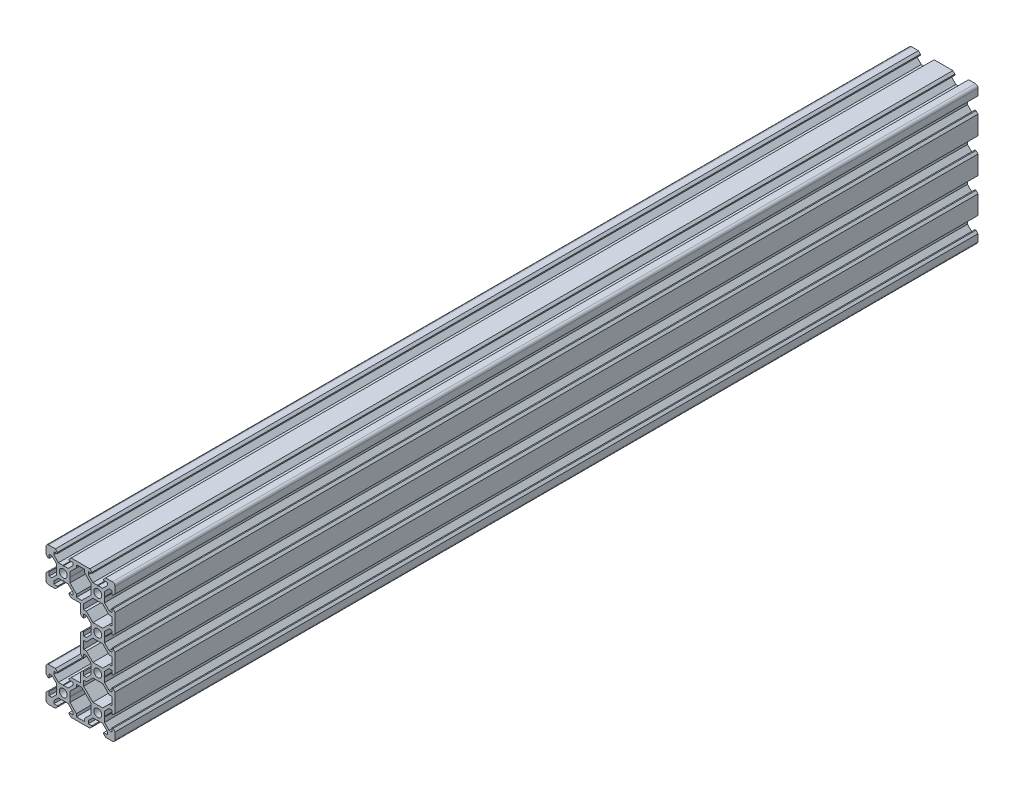
SolidWorks part; units mm, degrees
material "6063-T5"
ref_plane "Front Plane" through (0, 0, 0) normal (0, 0, 1) x (1, 0, 0)
ref_plane "Top Plane" through (0, 0, 0) normal (0, 1, 0) x (1, 0, 0)
ref_plane "Right Plane" through (0, 0, 0) normal (1, 0, 0) x (0, 0, -1)
sketch "Sketch1" plane through (0, 0, 0) normal (0, 0, 1) x (1, 0, 0)
  line L0 (0, 9.9766) -> (0, -9.9766) construction
  line L5 (-10, 10) -> (10, -10) construction
  line L6 (-10, -10) -> (10, 10) construction
  line L7 (-10.0451, 0) -> (10.0451, 0) construction
  line L8 (-4.578, 10) -> (-3.4, 8.822)
  line L9 (-3.4, 8.822) -> (-3.4, 8.202)
  line L10 (-3.4, 8.202) -> (-5.4992, 8.202)
  line L11 (-5.4992, 6.5612) -> (-2.84, 3.902)
  line L12 (-2.84, 3.902) -> (-0.21, 3.902)
  line L13 (-5.4992, 8.202) -> (-5.4992, 6.5612)
  line L14 (-10, 4.578) -> (-8.822, 3.4)
  line L15 (-8.822, 3.4) -> (-8.202, 3.4)
  line L16 (-8.202, 3.4) -> (-8.202, 5.4992)
  line L17 (-8.202, 5.4992) -> (-6.5612, 5.4992)
  line L18 (-6.5612, 5.4992) -> (-3.902, 2.84)
  line L19 (-3.902, 2.84) -> (-3.9017, 0.2097)
  line L20 (3.902, 2.84) -> (3.902, 0.21)
  line L21 (6.5612, 5.4992) -> (3.902, 2.84)
  line L26 (2.84, 3.902) -> (0.2097, 3.9017)
  line L27 (5.4992, 6.5612) -> (2.84, 3.902)
  line L28 (5.4992, 8.202) -> (5.4992, 6.5612)
  line L29 (3.4, 8.202) -> (5.4992, 8.202)
  line L30 (3.4, 8.822) -> (3.4, 8.202)
  line L31 (4.578, 10) -> (3.4, 8.822)
  line L32 (2.84, -3.902) -> (0.21, -3.902)
  line L33 (5.4992, -6.5612) -> (2.84, -3.902)
  line L34 (5.4992, -8.202) -> (5.4992, -6.5612)
  line L35 (3.4, -8.202) -> (5.4992, -8.202)
  line L36 (4.578, -10) -> (3.4, -8.822)
  line L37 (3.4, -8.822) -> (3.4, -8.202)
  line L38 (3.902, -2.84) -> (3.9017, -0.2097)
  line L39 (6.5612, -5.4992) -> (3.902, -2.84)
  line L44 (-3.902, -2.84) -> (-3.902, -0.21)
  line L45 (-6.5612, -5.4992) -> (-3.902, -2.84)
  line L46 (-8.202, -5.4992) -> (-6.5612, -5.4992)
  line L47 (-8.202, -3.4) -> (-8.202, -5.4992)
  line L48 (-10, -4.578) -> (-8.822, -3.4)
  line L49 (-8.822, -3.4) -> (-8.202, -3.4)
  line L50 (-2.84, -3.902) -> (-0.2097, -3.9017)
  line L51 (-5.4992, -6.5612) -> (-2.84, -3.902)
  line L52 (-5.4992, -8.202) -> (-5.4992, -6.5612)
  line L53 (-3.4, -8.202) -> (-5.4992, -8.202)
  line L54 (-3.4, -8.822) -> (-3.4, -8.202)
  line L55 (-4.578, -10) -> (-3.4, -8.822)
  line L56 (-0.21, 3.902) -> (0, 3.692)
  line L57 (0, 3.692) -> (0.2097, 3.9017)
  line L60 (0, -3.692) -> (-0.2097, -3.9017)
  line L61 (0.21, -3.902) -> (0, -3.692)
  line L62 (-3.692, 0) -> (-3.9017, 0.2097)
  line L63 (-3.902, -0.21) -> (-3.692, 0)
  line L64 (-8.5, 10) -> (-4.578, 10)
  line L65 (-10, 8.5) -> (-10, 4.578)
  line L66 (-10, -4.578) -> (-10, -8.5)
  line L67 (-8.5, -10) -> (-4.578, -10)
  line L68 (4.578, -10) -> (10, -10)
  line L71 (15.422, 10) -> (4.578, 10)
  line L80 (6.5612, -5.4992) -> (7.7124, -6.6505)
  line L82 (7.7124, -8.1789) -> (10, -8.1789)
  line L88 (7.7124, -6.6505) -> (7.7124, -8.1789)
  line L90 (8.202, -3.4) -> (8.202, -5.4992) [skipped]
  line L91 (8.202, -5.4992) -> (6.5612, -5.4992) [skipped]
  line L92 (8.822, -3.4) -> (8.202, -3.4) [skipped]
  line L93 (10, -4.578) -> (8.822, -3.4) [skipped]
  line L103 (10, 10) -> (10, -10) construction
  line L106 (10, 10) -> (30, -10) construction
  line L108 (10, -10) -> (30, 10) construction
  line L110 (10, -8.1789) -> (10.74, -8.1789)
  line L112 (10.74, -8.1789) -> (16.098, -2.8209)
  line L114 (11.8211, -10) -> (11.8211, -9.26)
  line L115 (11.8211, -9.26) -> (17.1791, -3.902)
  line L116 (6.5612, 5.4992) -> (7.6221, 6.5602)
  line L125 (7.6221, 6.5602) -> (7.6221, 8.2015)
  line L127 (7.6221, 8.2015) -> (12.3779, 8.2015)
  line L128 (8.202, 5.4992) -> (6.5612, 5.4992) [skipped]
  line L129 (8.202, 3.4) -> (8.202, 5.4992) [skipped]
  line L130 (8.822, 3.4) -> (8.202, 3.4) [skipped]
  line L131 (10, 4.578) -> (8.822, 3.4) [skipped]
  line L134 (16.098, 2.84) -> (16.098, -2.8209)
  line L137 (16.098, 3.902) -> (23.902, -3.902) construction
  line L138 (16.098, -3.902) -> (23.902, 3.902) construction
  line L140 (15.422, 10) -> (16.6, 8.822)
  line L141 (16.6, 8.822) -> (16.6, 8.202)
  line L142 (16.6, 8.202) -> (14.5008, 8.202)
  line L143 (14.5008, 8.202) -> (14.5008, 6.5612)
  line L144 (14.5008, 6.5612) -> (17.16, 3.902)
  line L145 (13.4388, 5.4992) -> (16.098, 2.84)
  line L146 (13.4388, 5.4992) -> (12.3779, 6.5602)
  line L147 (12.3779, 6.5602) -> (12.3779, 8.2015)
  line L148 (25.4992, 6.5612) -> (22.84, 3.902)
  line L149 (26.5612, 5.4992) -> (23.902, 2.84)
  line L150 (23.4, 8.822) -> (23.4, 8.202)
  line L151 (28.822, 3.4) -> (28.202, 3.4)
  line L152 (28.202, 3.4) -> (28.202, 5.4992)
  line L153 (30, 4.578) -> (28.822, 3.4)
  line L154 (28.202, 5.4992) -> (26.5612, 5.4992)
  line L155 (24.578, 10) -> (23.4, 8.822)
  line L156 (23.4, 8.202) -> (25.4992, 8.202)
  line L157 (25.4992, 8.202) -> (25.4992, 6.5612)
  line L158 (28.5, 10) -> (24.578, 10)
  line L159 (30, 8.5) -> (30, 4.578)
  line L160 (10.0451, 0) -> (29.9549, 0) construction
  line L161 (25.4992, -6.5612) -> (22.84, -3.902)
  line L167 (30, -15.422) -> (30, -4.578)
  line L168 (28.202, -5.4992) -> (26.5612, -5.4992)
  line L169 (30, -4.578) -> (28.822, -3.4)
  line L170 (28.202, -3.4) -> (28.202, -5.4992)
  line L171 (28.822, -3.4) -> (28.202, -3.4)
  line L172 (26.5612, -5.4992) -> (23.902, -2.84)
  line L173 (17.16, 3.902) -> (19.79, 3.902)
  line L174 (17.1791, -3.902) -> (22.84, -3.902)
  line L175 (23.902, -2.84) -> (23.902, -0.21)
  line L176 (23.898, -20.21) -> (23.898, -22.8606)
  line L177 (28.2471, -7.6231) -> (28.2471, -12.3769)
  line L178 (14.5008, -13.4388) -> (17.16, -16.098)
  line L179 (25.4992, -6.5612) -> (26.5612, -7.6231)
  line L180 (26.5612, -7.6231) -> (28.2471, -7.6231)
  line L181 (25.5443, -13.4388) -> (22.8851, -16.098)
  line L185 (23.898, -17.1394) -> (23.898, -19.79)
  line L186 (16.098, -16.1) -> (23.898, -23.9) construction
  line L187 (16.098, -23.9) -> (23.898, -16.1) construction
  line L188 (26.5367, -14.5008) -> (23.8775, -17.16)
  line L189 (28.822, -16.6) -> (28.1775, -16.6)
  line L190 (28.1775, -16.6) -> (28.1775, -14.5008)
  line L191 (30, -15.422) -> (28.822, -16.6)
  line L192 (28.1775, -14.5008) -> (26.5367, -14.5008)
  line L193 (26.6063, -12.3769) -> (28.2471, -12.3769)
  line L194 (25.5443, -13.4388) -> (26.6063, -12.3769)
  line L195 (14.5008, -13.4388) -> (13.3495, -12.2876)
  line L196 (11.8211, -12.2876) -> (11.8211, -10)
  line L197 (13.3495, -12.2876) -> (11.8211, -12.2876)
  line L198 (13.4388, -14.5008) -> (16.098, -17.16)
  line L199 (11.798, -14.5008) -> (13.4388, -14.5008)
  line L200 (11.798, -16.6) -> (11.798, -14.5008)
  line L201 (11.178, -16.6) -> (11.798, -16.6)
  line L202 (10, -15.422) -> (11.178, -16.6)
  line L203 (10, -15.422) -> (10, -10)
  line L204 (17.16, -16.098) -> (22.8851, -16.098)
  line L205 (3.902, 0.21) -> (3.9017, -0.2097)
  line L206 (16.098, -20) -> (23.898, -20) construction
  line L207 (13.4388, -25.4992) -> (16.098, -22.84)
  line L208 (11.798, -25.4992) -> (13.4388, -25.4992)
  line L209 (11.798, -23.4) -> (11.798, -25.4992)
  line L210 (11.178, -23.4) -> (11.798, -23.4)
  line L211 (10, -24.578) -> (11.178, -23.4)
  line L212 (10, -24.578) -> (10, -35.422)
  line L213 (11.8211, -27.7124) -> (11.8211, -32.2876)
  line L214 (13.3495, -27.7124) -> (11.8211, -27.7124)
  line L215 (14.5008, -26.5612) -> (13.3495, -27.7124)
  line L216 (14.5008, -26.5612) -> (17.16, -23.902)
  line L217 (25.5443, -26.5612) -> (22.8851, -23.902)
  line L218 (28.2471, -32.3769) -> (28.2471, -27.6231)
  line L219 (26.6063, -27.6231) -> (28.2471, -27.6231)
  line L220 (25.5443, -26.5612) -> (26.6063, -27.6231)
  line L221 (26.5367, -25.4992) -> (23.8775, -22.84)
  line L222 (28.1775, -25.4992) -> (26.5367, -25.4992)
  line L223 (28.822, -23.4) -> (28.1775, -23.4)
  line L224 (30, -24.578) -> (28.822, -23.4)
  line L225 (28.1775, -23.4) -> (28.1775, -25.4992)
  line L226 (30, -24.578) -> (30, -35.422)
  line L229 (17.16, -23.902) -> (22.8851, -23.902)
  line L230 (20, -3.902) -> (20, 3.902) construction
  line L231 (3.902, 0.21) -> (3.692, 0) [skipped]
  line L232 (3.692, 0) -> (3.9017, -0.2097) [skipped]
  line L233 (23.902, 0.21) -> (23.692, 0)
  line L234 (23.692, 0) -> (23.902, -0.21)
  line L235 (19.79, 3.902) -> (20, 3.692)
  line L236 (20, 3.692) -> (20.21, 3.902)
  line L237 (20.21, 3.902) -> (22.84, 3.902)
  line L238 (23.902, 0.21) -> (23.902, 2.84)
  line L239 (23.898, -19.79) -> (23.688, -20)
  line L240 (23.688, -20) -> (23.898, -20.21)
  line L241 (16.102, -19.79) -> (16.312, -20)
  line L242 (16.312, -20) -> (16.102, -20.21)
  line L243 (16.102, -19.79) -> (16.098, -17.16)
  line L244 (16.102, -20.21) -> (16.098, -22.84)
  line L246 (16.098, -40) -> (23.898, -40) construction
  line L247 (16.098, -36.1) -> (23.898, -43.9) construction
  line L248 (16.098, -43.9) -> (23.898, -36.1) construction
  line L250 (16.098, -56.098) -> (23.902, -63.902) construction
  line L251 (16.098, -63.902) -> (23.902, -56.098) construction
  line L252 (10, -50) -> (30, -70) construction
  line L253 (10, -70) -> (30, -50) construction
  line L254 (10, -70) -> (10, -50) construction
  line L256 (-10, -50) -> (10, -70) construction
  line L257 (-10, -70) -> (10, -50) construction
  line L259 (16.102, -39.79) -> (16.098, -37.16)
  line L260 (16.102, -40.21) -> (16.098, -42.84)
  line L261 (16.312, -40) -> (16.102, -39.79)
  line L262 (16.102, -40.21) -> (16.312, -40)
  line L263 (23.688, -40) -> (23.898, -39.79)
  line L264 (23.898, -40.21) -> (23.688, -40)
  line L265 (23.902, -60.21) -> (23.902, -62.84)
  line L266 (20.21, -63.902) -> (22.84, -63.902)
  line L267 (20, -63.692) -> (20.21, -63.902)
  line L268 (19.79, -63.902) -> (20, -63.692)
  line L269 (23.692, -60) -> (23.902, -59.79)
  line L270 (23.902, -60.21) -> (23.692, -60)
  line L271 (17.16, -36.098) -> (22.8851, -36.098)
  line L272 (28.1775, -36.6) -> (28.1775, -34.5008)
  line L273 (30, -35.422) -> (28.822, -36.6)
  line L274 (28.822, -36.6) -> (28.1775, -36.6)
  line L275 (28.1775, -34.5008) -> (26.5367, -34.5008)
  line L276 (26.5367, -34.5008) -> (23.8775, -37.16)
  line L277 (25.5443, -33.4388) -> (26.6063, -32.3769)
  line L278 (26.6063, -32.3769) -> (28.2471, -32.3769)
  line L279 (25.5443, -33.4388) -> (22.8851, -36.098)
  line L280 (14.5008, -33.4388) -> (17.16, -36.098)
  line L281 (14.5008, -33.4388) -> (13.3495, -32.2876)
  line L282 (13.3495, -32.2876) -> (11.8211, -32.2876)
  line L283 (10, -35.422) -> (11.178, -36.6)
  line L284 (11.178, -36.6) -> (11.798, -36.6)
  line L285 (11.798, -36.6) -> (11.798, -34.5008)
  line L286 (11.798, -34.5008) -> (13.4388, -34.5008)
  line L287 (13.4388, -34.5008) -> (16.098, -37.16)
  line L288 (3.902, -60.21) -> (3.9017, -59.7903)
  line L289 (17.16, -43.902) -> (22.8851, -43.902)
  line L290 (10, -44.578) -> (10, -50)
  line L291 (10, -44.578) -> (11.178, -43.4)
  line L292 (11.178, -43.4) -> (11.798, -43.4)
  line L293 (11.798, -43.4) -> (11.798, -45.4992)
  line L294 (11.798, -45.4992) -> (13.4388, -45.4992)
  line L295 (13.4388, -45.4992) -> (16.098, -42.84)
  line L296 (13.3495, -47.7124) -> (11.8211, -47.7124)
  line L297 (11.8211, -47.7124) -> (11.8211, -50)
  line L298 (14.5008, -46.5612) -> (13.3495, -47.7124)
  line L299 (25.5443, -46.5612) -> (26.6063, -47.6231)
  line L300 (26.6063, -47.6231) -> (28.2471, -47.6231)
  line L301 (28.1775, -45.4992) -> (26.5367, -45.4992)
  line L302 (30, -44.578) -> (28.822, -43.4)
  line L303 (28.1775, -43.4) -> (28.1775, -45.4992)
  line L304 (28.822, -43.4) -> (28.1775, -43.4)
  line L305 (26.5367, -45.4992) -> (23.8775, -42.84)
  line L306 (23.898, -42.8606) -> (23.898, -40.21)
  line L307 (25.5443, -46.5612) -> (22.8851, -43.902)
  line L308 (26.5612, -52.3769) -> (28.2471, -52.3769)
  line L309 (25.4992, -53.4388) -> (26.5612, -52.3769)
  line L310 (14.5008, -46.5612) -> (17.16, -43.902)
  line L311 (28.2471, -52.3769) -> (28.2471, -47.6231)
  line L312 (23.898, -39.79) -> (23.898, -37.1394)
  line L313 (23.902, -57.16) -> (23.902, -59.79)
  line L314 (17.1791, -56.098) -> (22.84, -56.098)
  line L315 (17.16, -63.902) -> (19.79, -63.902)
  line L316 (26.5612, -54.5008) -> (23.902, -57.16)
  line L317 (28.822, -56.6) -> (28.202, -56.6)
  line L318 (28.202, -56.6) -> (28.202, -54.5008)
  line L319 (30, -55.422) -> (28.822, -56.6)
  line L320 (28.202, -54.5008) -> (26.5612, -54.5008)
  line L321 (30, -44.578) -> (30, -55.422)
  line L322 (25.4992, -53.4388) -> (22.84, -56.098)
  line L323 (30, -68.5) -> (30, -64.578)
  line L324 (28.5, -70) -> (24.578, -70)
  line L325 (25.4992, -68.202) -> (25.4992, -66.5612)
  line L326 (23.4, -68.202) -> (25.4992, -68.202)
  line L327 (24.578, -70) -> (23.4, -68.822)
  line L328 (28.202, -65.4992) -> (26.5612, -65.4992)
  line L329 (30, -64.578) -> (28.822, -63.4)
  line L330 (28.202, -63.4) -> (28.202, -65.4992)
  line L331 (28.822, -63.4) -> (28.202, -63.4)
  line L332 (23.4, -68.822) -> (23.4, -68.202)
  line L333 (26.5612, -65.4992) -> (23.902, -62.84)
  line L334 (25.4992, -66.5612) -> (22.84, -63.902)
  line L335 (12.3779, -66.5602) -> (12.3779, -68.2015)
  line L336 (13.4388, -65.4992) -> (12.3779, -66.5602)
  line L337 (13.4388, -65.4992) -> (16.098, -62.84)
  line L338 (14.5008, -66.5612) -> (17.16, -63.902)
  line L339 (14.5008, -68.202) -> (14.5008, -66.5612)
  line L340 (16.6, -68.202) -> (14.5008, -68.202)
  line L341 (16.6, -68.822) -> (16.6, -68.202)
  line L342 (15.422, -70) -> (16.6, -68.822)
  line L343 (16.098, -62.84) -> (16.098, -57.1791)
  line L344 (7.6221, -68.2015) -> (12.3779, -68.2015)
  line L345 (7.6221, -66.5602) -> (7.6221, -68.2015)
  line L346 (6.5612, -65.4992) -> (7.6221, -66.5602)
  line L347 (11.8211, -50.74) -> (17.1791, -56.098)
  line L348 (11.8211, -50) -> (11.8211, -50.74)
  line L349 (10.74, -51.8211) -> (16.098, -57.1791)
  line L350 (10, -51.8211) -> (10.74, -51.8211)
  line L351 (7.7124, -53.3495) -> (7.7124, -51.8211)
  line L352 (7.7124, -51.8211) -> (10, -51.8211)
  line L353 (6.5612, -54.5008) -> (7.7124, -53.3495)
  line L354 (15.422, -70) -> (4.578, -70)
  line L355 (4.578, -50) -> (10, -50)
  line L356 (-8.5, -50) -> (-4.578, -50)
  line L357 (-10, -55.422) -> (-10, -51.5)
  line L358 (-10, -68.5) -> (-10, -64.578)
  line L359 (-8.5, -70) -> (-4.578, -70)
  line L360 (-3.902, -59.79) -> (-3.692, -60)
  line L361 (-3.692, -60) -> (-3.9017, -60.2097)
  line L362 (0.21, -56.098) -> (0, -56.308)
  line L363 (0, -56.308) -> (-0.2097, -56.0983)
  line L364 (0, -63.692) -> (0.2097, -63.9017)
  line L365 (-0.21, -63.902) -> (0, -63.692)
  line L366 (-4.578, -50) -> (-3.4, -51.178)
  line L367 (-3.4, -51.178) -> (-3.4, -51.798)
  line L368 (-3.4, -51.798) -> (-5.4992, -51.798)
  line L369 (-5.4992, -51.798) -> (-5.4992, -53.4388)
  line L370 (-5.4992, -53.4388) -> (-2.84, -56.098)
  line L371 (-2.84, -56.098) -> (-0.2097, -56.0983)
  line L372 (-8.822, -56.6) -> (-8.202, -56.6)
  line L373 (-10, -55.422) -> (-8.822, -56.6)
  line L374 (-8.202, -56.6) -> (-8.202, -54.5008)
  line L375 (-8.202, -54.5008) -> (-6.5612, -54.5008)
  line L376 (-6.5612, -54.5008) -> (-3.902, -57.16)
  line L377 (-3.902, -57.16) -> (-3.902, -59.79)
  line L378 (6.5612, -54.5008) -> (3.902, -57.16)
  line L379 (3.902, -57.16) -> (3.9017, -59.7903)
  line L380 (3.4, -51.178) -> (3.4, -51.798)
  line L381 (4.578, -50) -> (3.4, -51.178)
  line L382 (3.4, -51.798) -> (5.4992, -51.798)
  line L383 (5.4992, -51.798) -> (5.4992, -53.4388)
  line L384 (5.4992, -53.4388) -> (2.84, -56.098)
  line L385 (2.84, -56.098) -> (0.21, -56.098)
  line L386 (4.578, -70) -> (3.4, -68.822)
  line L387 (3.4, -68.822) -> (3.4, -68.202)
  line L388 (3.4, -68.202) -> (5.4992, -68.202)
  line L389 (5.4992, -68.202) -> (5.4992, -66.5612)
  line L390 (5.4992, -66.5612) -> (2.84, -63.902)
  line L391 (2.84, -63.902) -> (0.2097, -63.9017)
  line L392 (6.5612, -65.4992) -> (3.902, -62.84)
  line L393 (3.902, -62.84) -> (3.902, -60.21)
  line L394 (-3.902, -62.84) -> (-3.9017, -60.2097)
  line L395 (-6.5612, -65.4992) -> (-3.902, -62.84)
  line L396 (-8.202, -65.4992) -> (-6.5612, -65.4992)
  line L397 (-8.202, -63.4) -> (-8.202, -65.4992)
  line L398 (-8.822, -63.4) -> (-8.202, -63.4)
  line L399 (-10, -64.578) -> (-8.822, -63.4)
  line L400 (-5.4992, -68.202) -> (-5.4992, -66.5612)
  line L401 (-2.84, -63.902) -> (-0.21, -63.902)
  line L402 (-5.4992, -66.5612) -> (-2.84, -63.902)
  line L403 (-3.4, -68.202) -> (-5.4992, -68.202)
  line L404 (-3.4, -68.822) -> (-3.4, -68.202)
  line L405 (-4.578, -70) -> (-3.4, -68.822)
  circle A0 centre (0, 0) radius 2.3
  circle A1 centre (20, 0) radius 2.3
  circle A2 centre (19.998, -20) radius 2.3
  circle A3 centre (19.998, -40) radius 2.3
  circle A4 centre (20, -60) radius 2.3
  circle A5 centre (0, -60) radius 2.3
  arc A6 (-10, -51.5) -> (-8.5, -50) centre (-8.5, -51.5) cw
  arc A7 (-8.5, -70) -> (-10, -68.5) centre (-8.5, -68.5) cw
  arc A8 (28.5, -70) -> (30, -68.5) centre (28.5, -68.5) ccw
  arc A9 (28.5, 10) -> (30, 8.5) centre (28.5, 8.5) cw
  arc A10 (-10, -8.5) -> (-8.5, -10) centre (-8.5, -8.5) ccw
  arc A11 (-8.5, 10) -> (-10, 8.5) centre (-8.5, 8.5) ccw
  point P0 (0, 0)
  point P9 (0, 0)
  point P12 (0, 0)
  point P16 (20, 0)
  point P71 (0, 0)
  point P81 (0, 0)
  point P82 (0, 0)
  point P97 (10, 8.2015)
  point P153 (19.998, -20)
  point P199 (20, 0)
  point P211 (19.998, -20)
  point P388 (19.998, -40)
  point P389 (20, -60)
  point P390 (19.998, -40)
  point P391 (10, -68.2015)
  point P392 (0, -60)
  point P393 (0, -60)
  point P394 (0, -60)
  point P395 (20, -60)
  point P396 (0, -60)
  point P397 (0, -60)
  point P398 (0, -60)
  dimension "D11" = 4.6
  dimension "D28" = 1.5
  dimension "D2" = 20
  dimension "D3" = 45
  dimension "D4" = 3.4
  dimension "D5" = 0.21
  dimension "D6" = 0.62
  dimension "D7" = 4.3
  dimension "D8" = 2.84
  dimension "D9" = 4
  dimension "D10" = 4
  dimension "D12" = 90
  dimension "D13" = 1.6408
  dimension "D15" = 20
  dimension "D14" = 20
  dimension "D16" = 20
  dimension "D17" = 0.74
  dimension "D18" = 20
  dimension "D19" = 7.8
  dimension "D20" = 80
  dimension "D21" = 0.21
  dimension "D22" = 0.21
  dimension "D23" = 0.21
  dimension "D24" = 0.21
  dimension "D25" = 0.21
  dimension "D26" = 3.9
  dimension "D27" = 40
extrude "Boss-Extrude1" add sketch "Sketch1" against normal blind 500 contours L359 L405 L404 L403 L400 L402 L401 L365 L364 L391 L390 L389 L388 L387 L386 L354 L342 L341 L340 L339 L338 L315 L268 L267 L266 L334 L325 L326 L332 L327 L324 L323 L329 L331 L330 L328 L333 L265 L270 L269 L313 L316 L320 L318 L317 L319 L321 L302 L304 L303 L301
